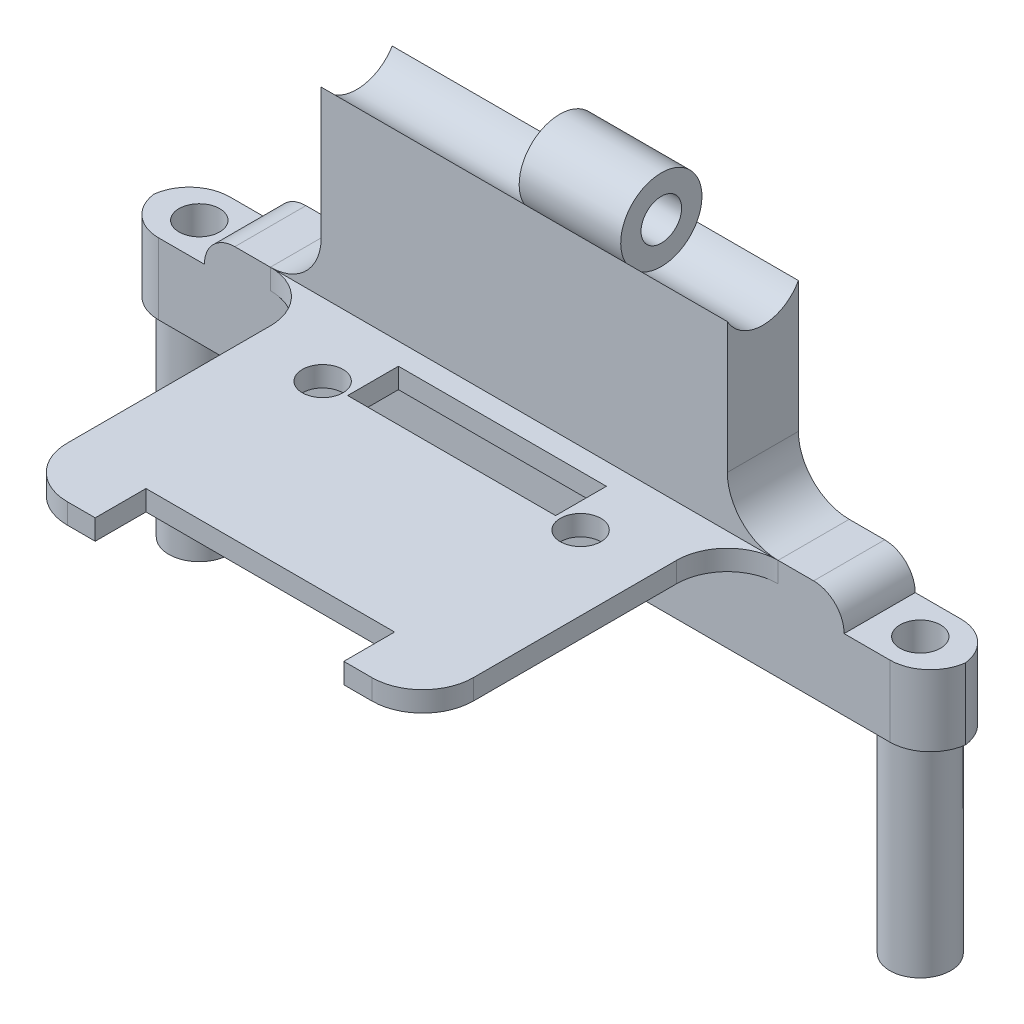
SolidWorks part; units mm, degrees
ref_plane "Front Plane" through (0, 0, 0) normal (0, 0, 1) x (1, 0, 0)
ref_plane "Top Plane" through (0, 0, 0) normal (0, 1, 0) x (1, 0, 0)
ref_plane "Right Plane" through (0, 0, 0) normal (1, 0, 0) x (0, 0, -1)
sketch "Sketch1" plane through (0, 0, 0) normal (0, 1, 0) x (1, 0, 0)
  line L1 (41.8203, 10.4118) -> (-38.1797, 10.4118)
  line L2 (41.8203, 10.4118) -> (41.8203, 3.4118)
  line L3 (41.8203, 3.4118) -> (-38.1797, 3.4118)
  line L4 (-38.1797, 10.4118) -> (-38.1797, 3.4118)
  dimension "D1" = 7
  dimension "D2" = 80
extrude "Boss-Extrude1" add sketch "Sketch1" along normal blind 30
sketch "Sketch2" plane through (0, 0, 0) normal (0, -1, 0) x (1, 0, 0)
  line L0 (41.8203, -3.4118) -> (41.8203, -10.4118) construction
  line L1 (-38.1797, -3.4118) -> (41.8203, -3.4118) construction
  line L2 (41.8203, -10.4118) -> (-38.1797, -10.4118) construction
  circle A0 centre (-33.6797, -6.9118) radius 3
  circle A1 centre (37.3203, -6.9118) radius 3
  circle A2 centre (-33.6797, -6.9118) radius 2
  circle A3 centre (37.3203, -6.9118) radius 2
  dimension "D1" = 6
  dimension "D2" = 6
  dimension "D3" = 71
  dimension "D4" = 4.5
  dimension "D5" = 3.5
  dimension "D6" = 3.5
  dimension "D7" = 4
  dimension "D8" = 4
extrude "Boss-Extrude2" add sketch "Sketch2" along normal blind 20
sketch "Sketch7" plane through (0, 0, -10.4118) normal (0, 0, -1) x (-1, 0, 0)
  line L0 (-41.8203, 0) -> (38.1797, 0) construction
  line L1 (-41.8203, 30) -> (-21.8203, 30)
  line L2 (-41.8203, 30) -> (-41.8203, 10)
  line L3 (-41.8203, 10) -> (-21.8203, 10)
  line L4 (-21.8203, 30) -> (-21.8203, 10)
  line L5 (38.1797, 30) -> (18.1797, 30)
  line L6 (38.1797, 30) -> (38.1797, 10)
  line L7 (38.1797, 10) -> (18.1797, 10)
  line L8 (18.1797, 30) -> (18.1797, 10)
  dimension "D1" = 10
  dimension "D2" = 10
  dimension "D3" = 40
  dimension "D4" = 20
extrude "Cut-Extrude1" cut sketch "Sketch7" against normal through all
sketch "Sketch9" plane through (-18.1797, 0, 0) normal (-1, 0, 0) x (0, 0, 1)
  line L0 (-3.4118, 30) -> (-10.4118, 30) construction
  circle A0 centre (-6.9118, 30) radius 4.1
  dimension "D1" = 8.2
extrude "Cut-Extrude2" cut sketch "Sketch9" against normal through all
sketch "Sketch11" plane through (21.8203, 0, 0) normal (1, 0, 0) x (0, 0, -1)
  circle A0 centre (6.9118, 29.8011) radius 4
  circle A1 centre (6.9118, 29.8011) radius 2
  dimension "D1" = 8
  dimension "D2" = 4
extrude "Boss-Extrude6" add sketch "Sketch11" against normal blind 20
fillet "Fillet1" radius 5 2 edges at (-18.1797, 10, -6.9118) (21.8203, 10, -6.9118)
fillet "Fillet2" radius 4 4 edges at (41.8203, 5, -10.4118) (41.8203, 5, -3.4118) (-38.1797, 5, -3.4118) (-38.1797, 5, -10.4118)
sketch "Sketch14" plane through (0, 0, -3.4118) normal (0, 0, 1) x (1, 0, 0)
  line L0 (-34.1797, 0) -> (37.8203, 0) construction
  line L1 (21.8203, 10) -> (-18.1797, 10)
  line L2 (21.8203, 10) -> (21.8203, 8)
  line L3 (21.8203, 8) -> (-18.1797, 8)
  line L4 (-18.1797, 10) -> (-18.1797, 8)
  line L6 (-18.1797, 27.8646) -> (-18.1797, 15) construction
  line L8 (21.8203, 15) -> (21.8203, 27.8646) construction
  dimension "D1" = 10
  dimension "D2" = 2
  dimension "D3" = 0
  dimension "D4" = 0
extrude "Boss-Extrude8" add sketch "Sketch14" along normal blind 30
fillet "Fillet4" radius 5 4 edges at (-18.1797, 9, 26.5882) (21.8203, 9, 26.5882) (21.8203, 9, -3.4118) (-18.1797, 9, -3.4118)
sketch "Sketch15" plane through (0, 10, 0) normal (0, 1, 0) x (1, 0, 0)
  circle A0 centre (-10.8897, -3.7282) radius 2
  circle A1 centre (14.5103, -3.7282) radius 2
  dimension "D1" = 4
  dimension "D2" = 4
extrude "Cut-Extrude3" cut sketch "Sketch15" against normal through all
sketch "Sketch16" plane through (0, 10, 0) normal (0, 1, 0) x (1, 0, 0)
  line L0 (17.0503, -3.1882) -> (17.0503, -24.5882) construction
  line L1 (-8.4297, -3.7282) -> (12.0503, -3.7282)
  line L2 (-8.4297, -3.7282) -> (-8.4297, 1.2718)
  line L3 (-8.4297, 1.2718) -> (12.0503, 1.2718)
  line L4 (12.0503, -3.7282) -> (12.0503, 1.2718)
  line L5 (-13.4297, -24.5882) -> (-13.4297, -3.1882) construction
  line L6 (16.8203, -26.5882) -> (-13.1797, -26.5882) construction
  line L7 (-10.4297, -21.5882) -> (14.0503, -21.5882)
  line L8 (-10.4297, -21.5882) -> (-10.4297, -26.5882)
  line L9 (-10.4297, -26.5882) -> (14.0503, -26.5882)
  line L10 (14.0503, -21.5882) -> (14.0503, -26.5882)
  circle A0 centre (-10.8897, -3.7282) radius 1.5 construction
  dimension "D1" = 0
  dimension "D2" = 5
  dimension "D3" = 5
  dimension "D4" = 5
  dimension "D5" = 3
  dimension "D6" = 3
  dimension "D7" = 5
  dimension "D8" = 0
extrude "Cut-Extrude4" cut sketch "Sketch16" against normal through all
extrude "Cut-Extrude5" cut sketch "Sketch11<2>" against normal blind 10
sketch "Sketch11<2>" plane through (21.8203, 0, 0) normal (1, 0, 0) x (0, 0, -1) same geometry as "Sketch11"
sketch "Sketch17" plane through (0, 0, 0) normal (0, -1, 0) x (1, 0, 0)
  circle A0 centre (37.3203, -6.9118) radius 2
  circle A1 centre (-33.6797, -6.9118) radius 2
  dimension "D1" = 4
  dimension "D2" = 4
extrude "Cut-Extrude6" cut sketch "Sketch17" against normal up to next
sketch "Sketch18" plane through (0, 10, 0) normal (0, 1, 0) x (1, 0, 0)
  line L6 (26.8203, 10.4118) -> (26.8203, 3.4118) construction
  line L9 (37.8203, 10.4118) -> (26.8203, 10.4118)
  line L10 (26.8203, 10.4118) -> (26.8203, 3.4118)
  line L11 (26.8203, 3.4118) -> (37.8203, 3.4118)
  line L12 (37.8203, 10.4118) -> (33.3203, 10.4118)
  line L13 (33.3203, 10.4118) -> (33.3203, 3.4118)
  line L14 (33.3203, 3.4118) -> (37.8203, 3.4118)
  line L16 (-23.1797, 3.4118) -> (-23.1797, 10.4118) construction
  line L19 (-34.1797, 3.4118) -> (-23.1797, 3.4118)
  line L20 (-23.1797, 3.4118) -> (-23.1797, 10.4118)
  line L21 (-23.1797, 10.4118) -> (-34.1797, 10.4118)
  line L22 (-34.1797, 3.4118) -> (-29.6797, 3.4118)
  line L23 (-29.6797, 3.4118) -> (-29.6797, 10.4118)
  line L24 (-29.6797, 10.4118) -> (-34.1797, 10.4118)
  arc A7 (37.8203, 3.4118) -> (41.789, 6.9118) centre (37.8203, 7.4118) ccw
  arc A8 (41.789, 6.9118) -> (37.8203, 10.4118) centre (37.8203, 6.4118) ccw
  arc A9 (37.8203, 3.4118) -> (41.789, 6.9118) centre (37.8203, 7.4118) ccw
  arc A10 (41.789, 6.9118) -> (37.8203, 10.4118) centre (37.8203, 6.4118) ccw
  arc A13 (-34.1797, 10.4118) -> (-38.1483, 6.9118) centre (-34.1797, 6.4118) ccw
  arc A14 (-38.1483, 6.9118) -> (-34.1797, 3.4118) centre (-34.1797, 7.4118) ccw
  arc A15 (-34.1797, 10.4118) -> (-38.1483, 6.9118) centre (-34.1797, 6.4118) ccw
  arc A16 (-38.1483, 6.9118) -> (-34.1797, 3.4118) centre (-34.1797, 7.4118) ccw
  dimension "D2" = 6.5
  dimension "D4" = 6.5
  dimension "D1" = 0
  dimension "D3" = 0
extrude "Cut-Extrude7" cut sketch "Sketch18" against normal blind 3
fillet "Fillet5" radius 3 2 edges at (-29.6797, 10, -6.9118) (33.3203, 10, -6.9118)
